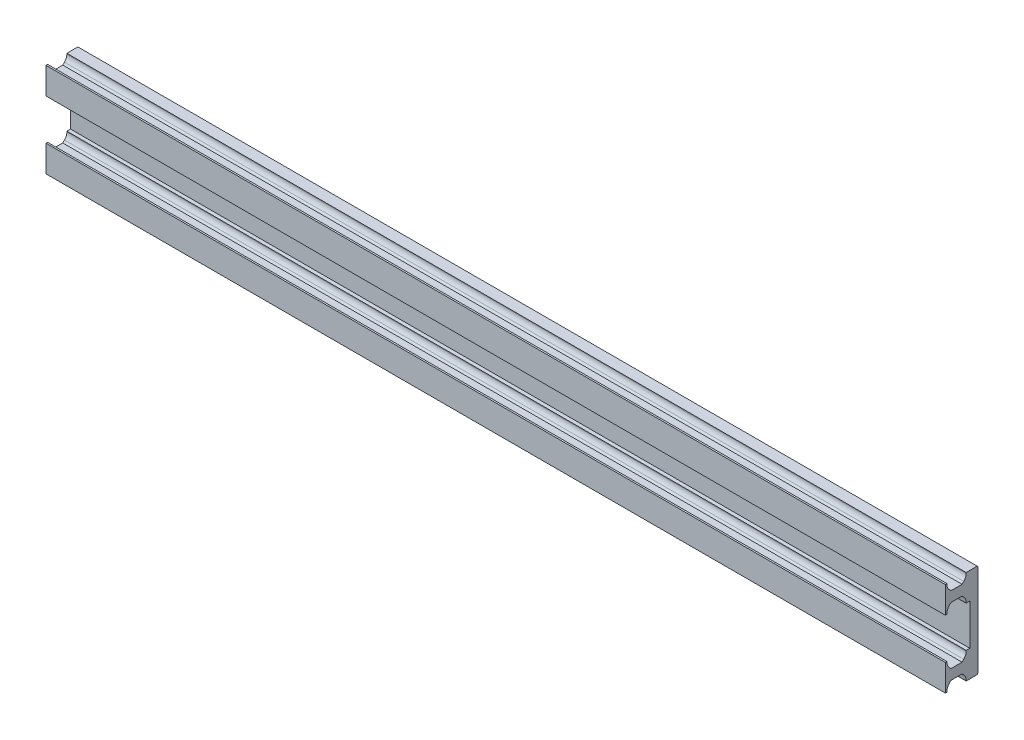
SolidWorks part; units mm, degrees
ref_plane "Front" through (0, 0, 0) normal (0, 0, 1) x (1, 0, 0)
ref_plane "Top" through (0, 0, 0) normal (0, 1, 0) x (1, 0, 0)
ref_plane "Right" through (0, 0, 0) normal (1, 0, 0) x (0, 0, -1)
sketch "Sketch1" plane through (0, 0, 0) normal (0, 0, 1) x (1, 0, 0)
  line L0 (-110, -4.5) -> (-110, 4.5) construction
  line L1 (110, 11.5) -> (-110, 11.5)
  line L2 (110, 11.5) -> (110, -11.5)
  line L3 (110, -11.5) -> (-110, -11.5)
  line L4 (-110, 11.5) -> (-110, -11.5)
  line L5 (110, 11.5) -> (-110, -11.5) construction
  line L6 (110, -11.5) -> (-110, 11.5) construction
  line L8 (110, 4.5) -> (-110, 4.5) construction
  point P0 (0, 0)
  dimension "D1" = 7
extrude "Boss-Extrude1" add sketch "Sketch1" against normal blind 2
sketch "Sketch2" plane through (0, 0, 0) normal (0, 0, 1) x (1, 0, 0)
  line L0 (-110, 11.5) -> (-110, -11.5) construction
  line L1 (110, 11.5) -> (-110, 11.5)
  line L2 (110, 11.5) -> (110, 5)
  line L3 (110, 5) -> (-110, 5)
  line L4 (-110, 11.5) -> (-110, 5)
  line L5 (110, -11.5) -> (110, 11.5) construction
  line L6 (110, -11.5) -> (-110, -11.5)
  line L7 (110, -11.5) -> (110, -5)
  line L8 (110, -5) -> (-110, -5)
  line L9 (-110, -11.5) -> (-110, -5)
  line L11 (110, 4.5) -> (-110, 4.5) construction
  dimension "D1" = 0.5
extrude "Boss-Extrude2" add sketch "Sketch2" along normal offset from surface (6 mm away) 1
ref_plane "Center of Slots" through (0, 8.25, 0) normal (0, -1, 0) x (-1, 0, 0)
sketch "Sketch5" plane through (0, 0, 0) normal (1, 0, 0) x (0, 0, -1)
  line L16 (-1.9, 7) -> (-4.6, 7)
  line L17 (-1.9, 7) -> (-4.6, 7)
  line L18 (-1.4858, 6.5858) -> (-1.9, 7)
  line L19 (-1.4858, 6.5858) -> (-1.9, 7)
  line L20 (-0.9, 4.3284) -> (-0.9, 5.1716)
  line L21 (-0.9, 4.3284) -> (-0.9, 5.1716)
  line L22 (-1.9, 2.5) -> (-1.4858, 2.9142)
  line L23 (-1.9, 2.5) -> (-1.4858, 2.9142)
  line L24 (-4.6, 2.5) -> (-1.9, 2.5)
  line L25 (-4.6, 2.5) -> (-1.9, 2.5)
  line L26 (-5.0142, 2.9142) -> (-4.6, 2.5)
  line L27 (-5.0142, 2.9142) -> (-4.6, 2.5)
  line L28 (-5.6, 5.1716) -> (-5.6, 4.3284)
  line L29 (-5.6, 5.1716) -> (-5.6, 4.3284)
  line L30 (-4.6, 7) -> (-5.0142, 6.5858)
  line L31 (-4.6, 7) -> (-5.0142, 6.5858)
  arc A12 (-0.9, 5.1716) -> (-1.4858, 6.5858) centre (-2.9, 5.1716) ccw
  arc A13 (-0.9, 5.1716) -> (-1.4858, 6.5858) centre (-2.9, 5.1716) ccw
  arc A14 (-1.4858, 2.9142) -> (-0.9, 4.3284) centre (-2.9, 4.3284) ccw
  arc A15 (-1.4858, 2.9142) -> (-0.9, 4.3284) centre (-2.9, 4.3284) ccw
  arc A16 (-5.6, 4.3284) -> (-5.0142, 2.9142) centre (-3.6, 4.3284) ccw
  arc A17 (-5.6, 4.3284) -> (-5.0142, 2.9142) centre (-3.6, 4.3284) ccw
  arc A18 (-5.0142, 6.5858) -> (-5.6, 5.1716) centre (-3.6, 5.1716) ccw
  arc A19 (-5.0142, 6.5858) -> (-5.6, 5.1716) centre (-3.6, 5.1716) ccw
  dimension "D1" = 0
extrude "Middle Slot" cut sketch "Sketch5" against normal through all both and the other way through all
mirror "Middle Slots" about plane through (0, 0, 0) normal (0, 1, 0) of "Middle Slot"
sketch "Sketch7" plane through (0, 0, 0) normal (1, 0, 0) x (0, 0, -1)
  line L8 (-1.875, 13.975) -> (-4.625, 13.975)
  line L9 (-1.4858, 13.5858) -> (-1.875, 13.975)
  line L10 (-0.9, 11.3284) -> (-0.9, 12.1716)
  line L11 (-1.9, 9.5) -> (-1.4858, 9.9142)
  line L12 (-4.6, 9.5) -> (-1.9, 9.5)
  line L13 (-5.0142, 9.9142) -> (-4.6, 9.5)
  line L14 (-5.6, 12.1716) -> (-5.6, 11.3284)
  line L15 (-4.625, 13.975) -> (-5.0142, 13.5858)
  line L16 (-1.875, 13.975) -> (-4.625, 13.975)
  line L17 (-1.4858, 13.5858) -> (-1.875, 13.975)
  line L18 (-0.9, 11.3284) -> (-0.9, 12.1716)
  line L19 (-1.9, 9.5) -> (-1.4858, 9.9142)
  line L20 (-4.6, 9.5) -> (-1.9, 9.5)
  line L21 (-5.0142, 9.9142) -> (-4.6, 9.5)
  line L22 (-5.6, 12.1716) -> (-5.6, 11.3284)
  line L23 (-4.625, 13.975) -> (-5.0142, 13.5858)
  arc A4 (-0.9, 12.1716) -> (-1.4858, 13.5858) centre (-2.9, 12.1716) ccw
  arc A5 (-1.4858, 9.9142) -> (-0.9, 11.3284) centre (-2.9, 11.3284) ccw
  arc A6 (-5.6, 11.3284) -> (-5.0142, 9.9142) centre (-3.6, 11.3284) ccw
  arc A7 (-5.0142, 13.5858) -> (-5.6, 12.1716) centre (-3.6, 12.1716) ccw
  arc A8 (-0.9, 12.1716) -> (-1.4858, 13.5858) centre (-2.9, 12.1716) ccw
  arc A9 (-1.4858, 9.9142) -> (-0.9, 11.3284) centre (-2.9, 11.3284) ccw
  arc A10 (-5.6, 11.3284) -> (-5.0142, 9.9142) centre (-3.6, 11.3284) ccw
  arc A11 (-5.0142, 13.5858) -> (-5.6, 12.1716) centre (-3.6, 12.1716) ccw
  dimension "D1" = 0
extrude "Top Slot" cut sketch "Sketch7" against normal through all both and the other way through all
mirror "Top Slots" about plane through (0, 0, 0) normal (0, 1, 0) of "Top Slot"
chamfer "Deburs" distance 0.2 angle 45 2 edges at (0, -11.5, -2) (0, 11.5, -2)
